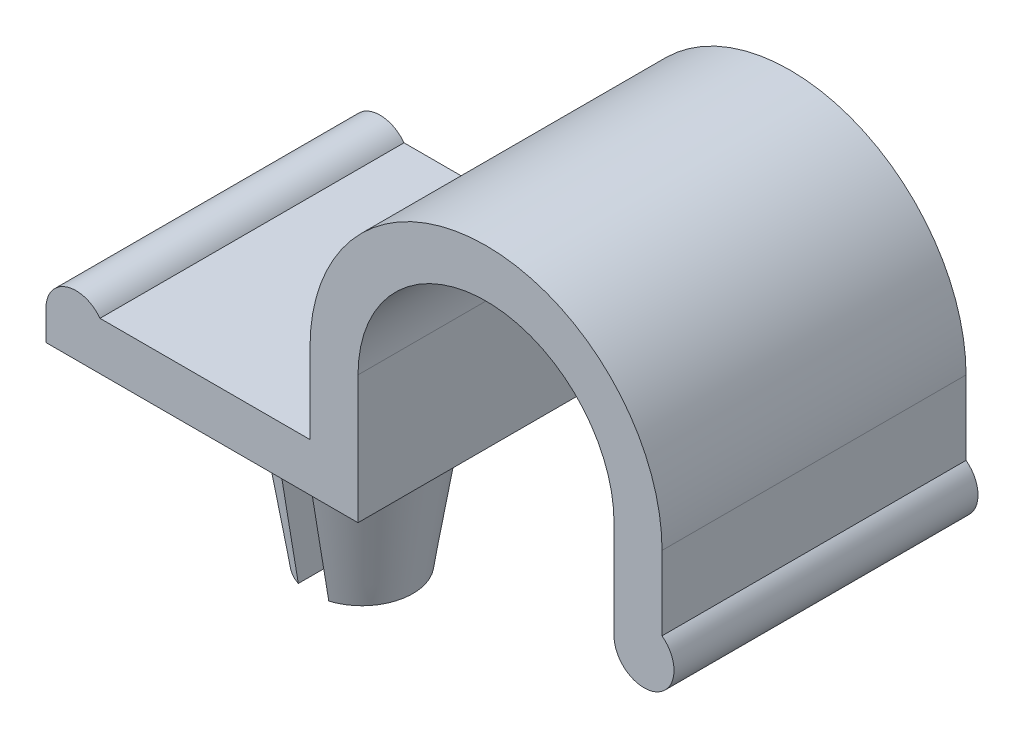
SolidWorks part; units mm, degrees
ref_plane "Front" through (0, 0, 0) normal (0, 0, 1) x (1, 0, 0)
ref_plane "Top" through (0, 0, 0) normal (0, 1, 0) x (1, 0, 0)
ref_plane "Right" through (0, 0, 0) normal (1, 0, 0) x (0, 0, -1)
sketch "Sketch1" plane through (0, 0, 0) normal (0, 0, 1) x (1, 0, 0)
  line L0 (-9.65, -2) -> (-4.4, -2)
  line L1 (4.4, 0) -> (4.4, -1.85)
  line L2 (3.2, 0) -> (3.2, -2.45)
  line L3 (-3.2, 0) -> (-3.2, -3.2)
  line L4 (-4.4, 0) -> (-4.4, -2)
  line L5 (-6.9, -2) -> (-6.9, -8.7588) construction
  line L6 (-3.2, -3.2) -> (-11, -3.2)
  line L7 (-11, -3.2) -> (-11, -2.45)
  line L8 (-9.65, -2) -> (-9.65, -3.2) construction
  line L9 (3.2, 0) -> (4.4, 0) construction
  arc A0 (3.2, 0) -> (-3.2, 0) centre (0, 0) ccw
  arc A1 (4.4, 0) -> (-4.4, 0) centre (0, 0) ccw
  arc A2 (3.2, -2.45) -> (4.4, -1.85) centre (3.95, -2.45) ccw
  arc A3 (-9.65, -2) -> (-11, -2.45) centre (-10.25, -2.45) ccw
  dimension "D1" = 6.4
  dimension "D2" = 1.2
  dimension "D4" = 0.75
  dimension "D6" = 15.7
  dimension "D3" = 7.6
  dimension "D8" = 6.9
  dimension "D9" = 4.1
extrude "Base-Extrude" add sketch "Sketch1" along normal mid plane 7.6
sketch "Sketch4" plane through (0, 0, 0) normal (0, 0, 1) x (1, 0, 0)
  line L0 (-6.9, -3.2) -> (-6.9, -7.851)
  line L2 (-6.9, -7.851) -> (-5.63, -7.851)
  line L3 (-6.9, -3.2) -> (-6.9, -2) construction
  line L4 (-5.15, -4.851) -> (-5.4, -4.851)
  line L5 (-5.4, -4.851) -> (-5.4, -3.2)
  line L6 (-5.4, -3.2) -> (-6.9, -3.2)
  line L8 (-5.15, -4.851) -> (-5.63, -7.851)
  line L9 (-11, -3.2) -> (-3.2, -3.2) construction
  dimension "D2" = 3
  dimension "D3" = 1.651
  dimension "D4" = 3
  dimension "D5" = 1.27
  dimension "D6" = 3.5
revolve "Boss-Revolve1" add sketch "Sketch4" angle 360 about L3
sketch "Sketch5" plane through (0, 0, 0) normal (0, 0, 1) x (1, 0, 0)
  line L0 (-8.17, -7.851) -> (-5.63, -7.851) construction
  line L1 (-7.281, -7.851) -> (-6.519, -7.851)
  line L2 (-7.281, -7.851) -> (-7.281, -3.787)
  line L3 (-6.9, -2) -> (-6.9, -8.7588) construction
  line L4 (-6.519, -7.851) -> (-6.519, -3.787)
  arc A0 (-6.519, -3.787) -> (-7.281, -3.787) centre (-6.9, -3.787) ccw
  dimension "D1" = 0.762
  dimension "D3" = 4.064
extrude "Cut-Extrude1" cut sketch "Sketch5" against normal through all and the other way through all
sketch "Sketch6" plane through (0, 0, 3.8) normal (0, 0, 1) x (1, 0, 0)
  point P0 (0, 0)
sketch "Sketch7" plane through (0, 0, -3.8) normal (0, 0, -1) x (-1, 0, 0)
  point P0 (0, 0)
ref_axis "Clip Axis" through (0, 0, 3.8) along (0, 0, -1)
other "RPoint1"
ref_axis "Axis1" through (0, 0, -1.2) along (0, 0, 1)
other "RPoint2"
ref_axis "Axis2" through (0, 0, 1.2) along (0, 0, -1)
sketch "FilterSketch" plane through (0, 0, 0) normal (0, 0, 1) x (1, 0, 0)
  circle A0 centre (0, 0) radius 3.2
  circle A1 centre (0, 0) radius 3.2
  circle A2 centre (0, 0) radius 2.35
  dimension "NominalDiameter" = 6.4
  dimension "InnerDiameter" = 4.7
  dimension "OuterDiameter" = 6.4
ref_axis "Axis of Rotation" through (-6.9, -3.2, 0) along (0, -1, 0)
